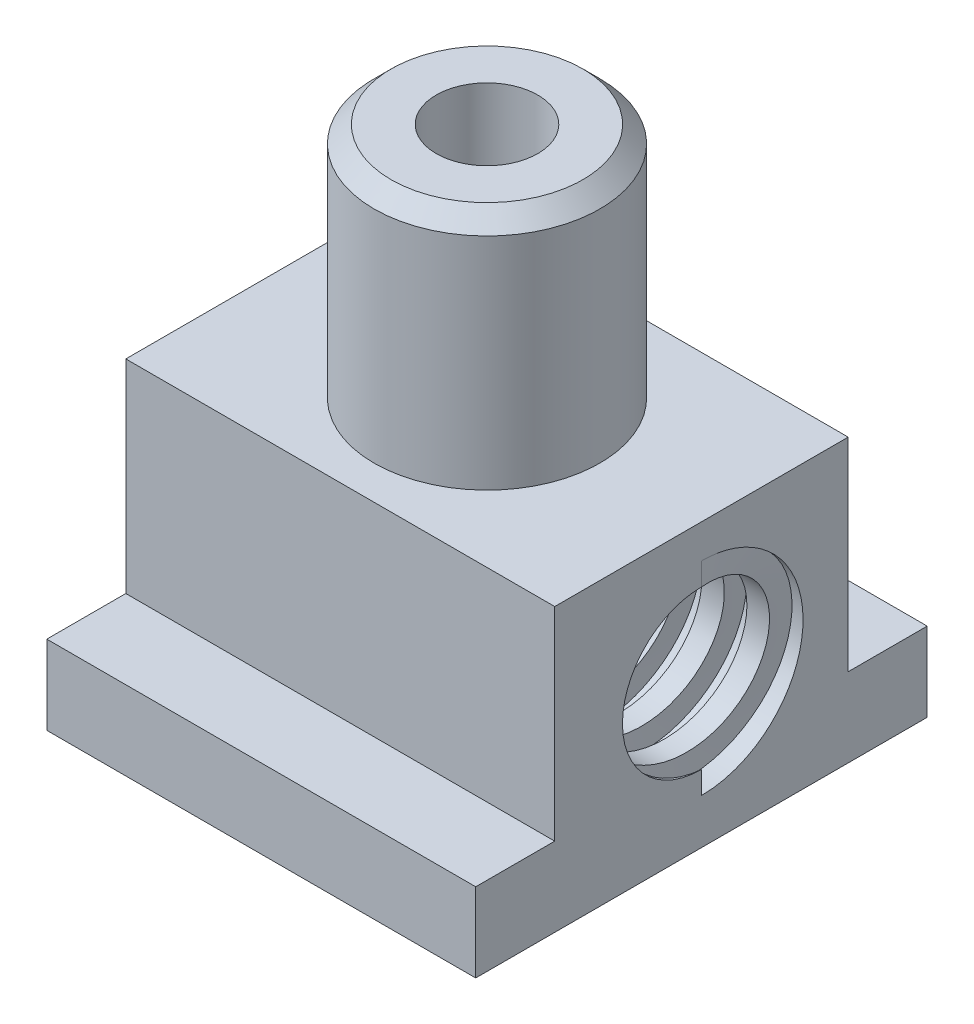
SolidWorks part; units mm, degrees
material "45"
ref_plane "前视基准面" through (0, 0, 0) normal (0, 0, 1) x (1, 0, 0)
ref_plane "上视基准面" through (0, 0, 0) normal (0, 1, 0) x (1, 0, 0)
ref_plane "右视基准面" through (0, 0, 0) normal (1, 0, 0) x (0, 0, -1)
sketch "草图1" plane through (0, 0, 0) normal (1, 0, 0) x (0, 0, -1)
  line L0 (0, 0) -> (0, 94.0587) construction
  line L1 (-20, 0) -> (20, 0)
  line L2 (20, 0) -> (20, 7)
  line L3 (20, 7) -> (13, 7)
  line L4 (13, 7) -> (13, 25)
  line L5 (13, 25) -> (-13, 25)
  line L6 (-13, 7) -> (-13, 25)
  line L7 (-20, 7) -> (-13, 7)
  line L8 (-20, 0) -> (-20, 7)
  point P9 (0, 25)
  dimension "D1" = 40
  dimension "D2" = 26
  dimension "D3" = 7
  dimension "D4" = 25
extrude "凸台-拉伸1" add sketch "草图1" along normal mid plane 38
sketch "草图3" plane through (-19, 0, 0) normal (-1, 0, 0) x (0, 0, 1)
  line L0 (0, -0.6049) -> (0, 20.9201) construction
  line L1 (13, 7) -> (20, 7) construction
  circle A0 centre (0, 13) radius 7
  dimension "D1" = 14
  dimension "D2" = 6
extrude "切除-拉伸1" cut sketch "草图3" against normal through all
sketch "草图4" plane through (0, 25, 0) normal (0, 1, 0) x (1, 0, 0)
  circle A0 centre (0, 0) radius 10
  dimension "D1" = 20
extrude "凸台-拉伸2" add sketch "草图4" along normal blind 21
chamfer "倒角1" distance 1.5 angle 45 1 edges at (0, 46, 10)
hole_wizard "M10x1.0 螺纹孔1" positions "草图6" profile "草图5" tap size "M10x1.0" standard "GB"
sketch "草图6" plane through (0, 46, 0) normal (0, 1, 0) x (-1, 0, 0)
  point P0 (0, 0)
sketch "草图5" plane through (0, 46, 0) normal (1, 0, 0) x (0, 0, 1)
  line L0 (0, 0) -> (0, 24.7039)
  line L1 (0, 24.7039) -> (4.5, 22)
  line L2 (4.5, 22) -> (4.5, 0)
  line L5 (4.5, 0) -> (0, 0)
  line L10 (0, 24.7039) -> (-4.5, 22) construction
  line L11 (0, -6.35) -> (0, 107.95) construction
  dimension "螺纹孔钻头直径" = 9
  dimension "螺纹孔钻头深度" = 22
  dimension "导头角度" = 118
cosmetic thread "孔螺蚊线1" parameters "D1"=17, "D2"=10
sketch "草图7" plane through (19, 0, 0) normal (1, 0, 0) x (0, 0, -1)
  circle A0 centre (0, 13) radius 7 construction
  circle A1 centre (0, 13) radius 7
curve "螺旋线/涡状线1" pitch 4 height 38 radius 7 centre (19, 13, 0) axis (-1, 0, 0) start towards (0, 0, -1)
ref_plane "基准面1" through (0, 13, 0) normal (0, 1, 0) x (-1, 0, 0)
sketch "草图9" plane through (0, 13, 0) normal (0, 1, 0) x (-1, 0, 0)
  line L0 (-20, -9) -> (-20, -7)
  line L1 (-20, -7) -> (-18, -7)
  line L2 (-18, -7) -> (-18, -9)
  line L3 (-18, -9) -> (-20, -9)
  line L4 (-19, -13) -> (-19, 13) construction
  line L5 (-19, -13) -> (-19, 13) construction
  line L6 (0, 0) -> (-21.7795, 0) construction
  dimension "D1" = 2
  dimension "D2" = 2
  dimension "D3" = 14
sweep "切除-扫描2" cut profiles "草图9" path "螺旋线/涡状线1" align with end faces yes
